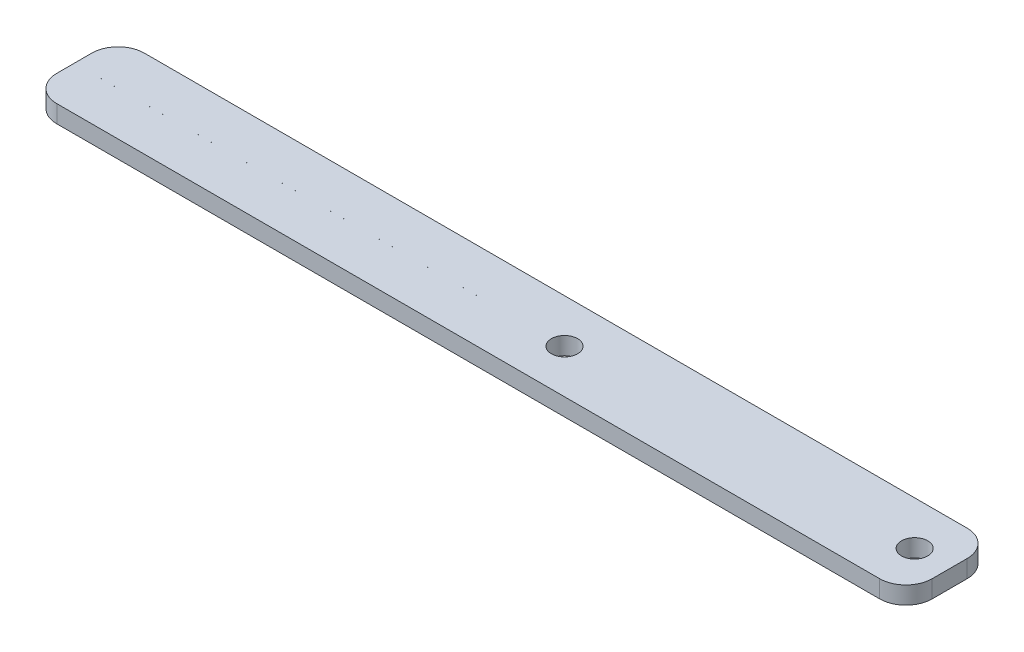
SolidWorks part; units mm, degrees
ref_plane "Front Plane" through (0, 0, 0) normal (0, 0, 1) x (1, 0, 0)
ref_plane "Top Plane" through (0, 0, 0) normal (0, 1, 0) x (1, 0, 0)
ref_plane "Right Plane" through (0, 0, 0) normal (1, 0, 0) x (0, 0, -1)
sketch "Sketch1" plane through (0, 0, 0) normal (0, 1, 0) x (1, 0, 0)
  line L1 (-50, 5) -> (50, 5)
  line L2 (-50, 5) -> (-50, -5)
  line L3 (-50, -5) -> (50, -5)
  line L4 (50, 5) -> (50, -5)
  line L5 (-50, 5) -> (50, -5) construction
  line L6 (-50, -5) -> (50, 5) construction
  point P0 (0, 0)
  dimension "D1" = 10
  dimension "D2" = 100
extrude "Boss-Extrude1" add sketch "Sketch1" along normal blind 2
sketch "Sketch2" plane through (0, 2, 0) normal (0, 1, 0) x (1, 0, 0)
  line L0 (26.3156, 5) -> (26.3156, -5) construction
  line L1 (-50, -5) -> (50, -5) construction
  line L2 (-50, 5) -> (-50, -5) construction
  line L4 (-3, 0.0005) -> (-50, 0.0005)
  line L5 (-3, 0.0005) -> (-3, -0.0005)
  line L6 (-3, -0.0005) -> (-50, -0.0005)
  line L7 (-50, 0.0005) -> (-50, -0.0005)
  line L8 (-3, 0.0005) -> (-50, -0.0005) construction
  line L9 (-3, -0.0005) -> (-50, 0.0005) construction
  point P0 (-26.5, 0)
  point P10 (26.3156, 0)
  point P14 (-50, 0)
  dimension "D1" = 47
  dimension "D2" = 0.001
fillet "Fillet1" radius 3 4 edges at (50, 1, 5) (50, 1, -5) (-50, 1, -5) (-50, 1, 5)
hole_wizard "Ø3.0mm Dowel Hole1" positions "Sketch3" profile "Sketch5" hole size "Ø3.0" standard "ISO" end condition through all
sketch "Sketch3" plane through (0, 2, 0) normal (0, 1, 0) x (1, 0, 0)
  line L0 (50, -2) -> (50, 2) construction
  point P0 (46, 0)
  point P5 (6, 0)
  point P8 (0, 0)
  point P9 (0, 0)
  dimension "D1" = 40
  dimension "D2" = 4
sketch "Sketch5" plane through (46, 2, 0) normal (1, 0, 0) x (0, 0, 1)
  line L0 (0, 0) -> (0, 2)
  line L1 (0, 2) -> (1.5, 2)
  line L2 (1.5, 2) -> (1.5, 0)
  line L5 (1.5, 0) -> (0, 0)
  line L11 (0, -22.0399) -> (0, 107.95) construction
  dimension "Thru Hole Dia." = 3
  dimension "Thru Hole Depth" = 2
extrude "Cut-Extrude1" cut sketch "Sketch2" against normal blind 10
